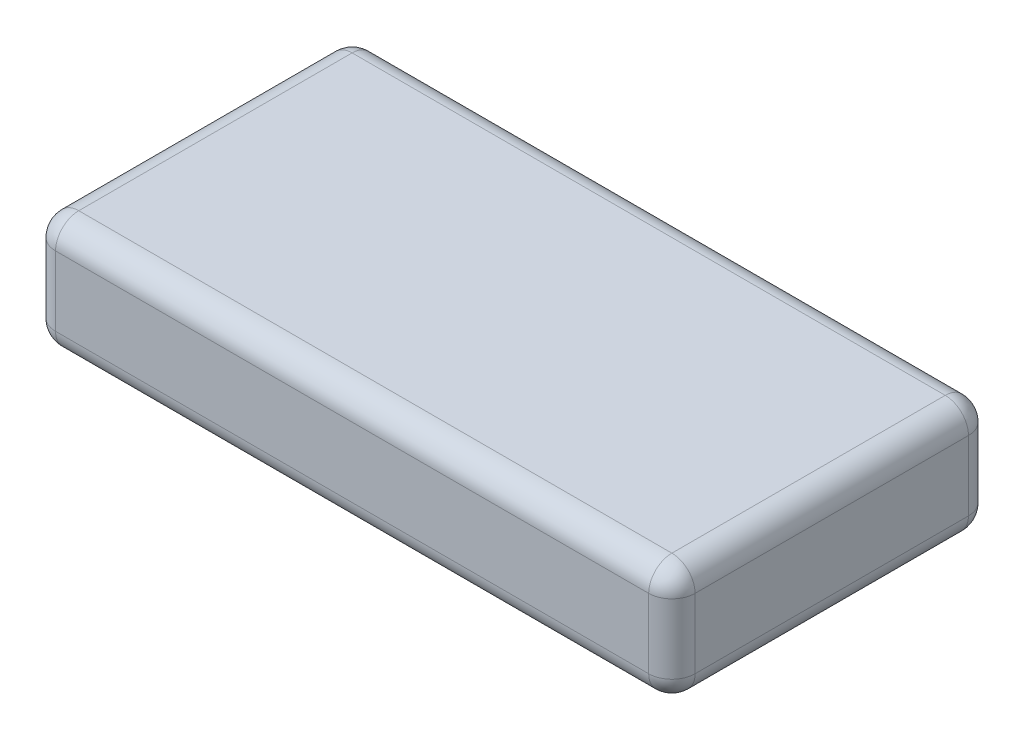
SolidWorks part; units mm, degrees
ref_plane "Front Plane" through (0, 0, 0) normal (0, 0, 1) x (1, 0, 0)
ref_plane "Top Plane" through (0, 0, 0) normal (0, 1, 0) x (1, 0, 0)
ref_plane "Right Plane" through (0, 0, 0) normal (1, 0, 0) x (0, 0, -1)
sketch "Sketch1" plane through (0, 0, 0) normal (0, 1, 0) x (1, 0, 0)
  line L1 (-26.6751, 23.1598) -> (43.3249, 23.1598)
  line L2 (-26.6751, 23.1598) -> (-26.6751, -11.8402)
  line L3 (-26.6751, -11.8402) -> (43.3249, -11.8402)
  line L4 (43.3249, 23.1598) -> (43.3249, -11.8402)
  dimension "D1" = 70
  dimension "D2" = 35
extrude "Boss-Extrude1" add sketch "Sketch1" along normal blind 12.7
fillet "Fillet1" radius 2.54 12 edges at (43.3249, 6.35, 11.8402) (8.3249, 0, 11.8402) (43.3249, 0, -5.6598) (-26.6751, 6.35, 11.8402) (-26.6751, 0, -5.6598) (43.3249, 6.35, -23.1598) (-26.6751, 6.35, -23.1598) (8.3249, 0, -23.1598) (8.3249, 12.7, -23.1598) (43.3249, 12.7, -5.6598) (8.3249, 12.7, 11.8402) (-26.6751, 12.7, -5.6598)
